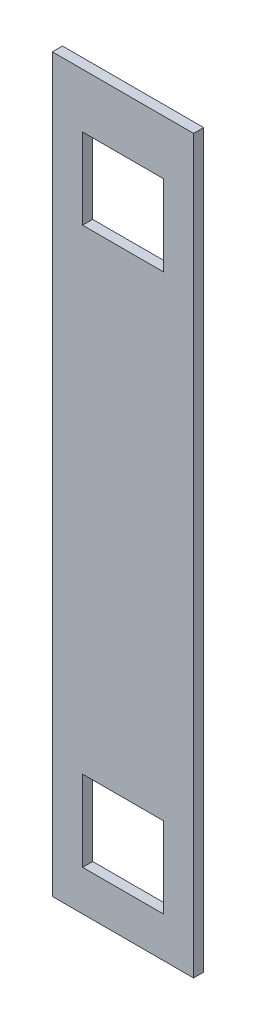
SolidWorks part; units mm, degrees
material "Oak"
ref_plane "Front Plane" through (0, 0, 0) normal (0, 0, 1) x (1, 0, 0)
ref_plane "Top Plane" through (0, 0, 0) normal (0, 1, 0) x (1, 0, 0)
ref_plane "Right Plane" through (0, 0, 0) normal (1, 0, 0) x (0, 0, -1)
sketch "Sketch1" plane through (0, 0, 0) normal (0, 0, 1) x (1, 0, 0)
  line L1 (-88.9, -460.375) -> (88.9, -460.375)
  line L2 (-88.9, -460.375) -> (-88.9, 460.375)
  line L3 (-88.9, 460.375) -> (88.9, 460.375)
  line L4 (88.9, -460.375) -> (88.9, 460.375)
  line L5 (-88.9, -460.375) -> (88.9, 460.375) construction
  line L6 (-88.9, 460.375) -> (88.9, -460.375) construction
  point P0 (0, 0)
  dimension "D1" = 920.75
  dimension "D2" = 177.8
extrude "Boss-Extrude1" add sketch "Sketch1" along normal blind 12.7
sketch "Sketch2" plane through (0, 0, 0) normal (0, 0, -1) x (-1, 0, 0)
  line L0 (-50.8, -409.575) -> (-88.9, -409.575) construction
  line L1 (-50.8, -307.975) -> (50.8, -307.975)
  line L2 (-50.8, -307.975) -> (-50.8, -409.575)
  line L3 (-50.8, -409.575) -> (50.8, -409.575)
  line L4 (50.8, -307.975) -> (50.8, -409.575)
  line L5 (-88.9, -460.375) -> (-88.9, 460.375) construction
  line L6 (50.8, -409.575) -> (88.9, -409.575) construction
  line L7 (88.9, 460.375) -> (88.9, -460.375) construction
  line L8 (88.9, -460.375) -> (-88.9, -460.375) construction
  line L9 (-50.8, 392.025) -> (-50.8, 290.425)
  line L10 (-50.8, 392.025) -> (50.8, 392.025)
  line L11 (50.8, 392.025) -> (50.8, 290.425)
  line L12 (-50.8, 290.425) -> (50.8, 290.425)
  dimension "D1" = 101.6
  dimension "D2" = 50.8
  dimension "D3" = 101.6
  dimension "D5" = 700
  dimension "D4" = 2
extrude "Cut-Extrude1" cut sketch "Sketch2" against normal up to next
